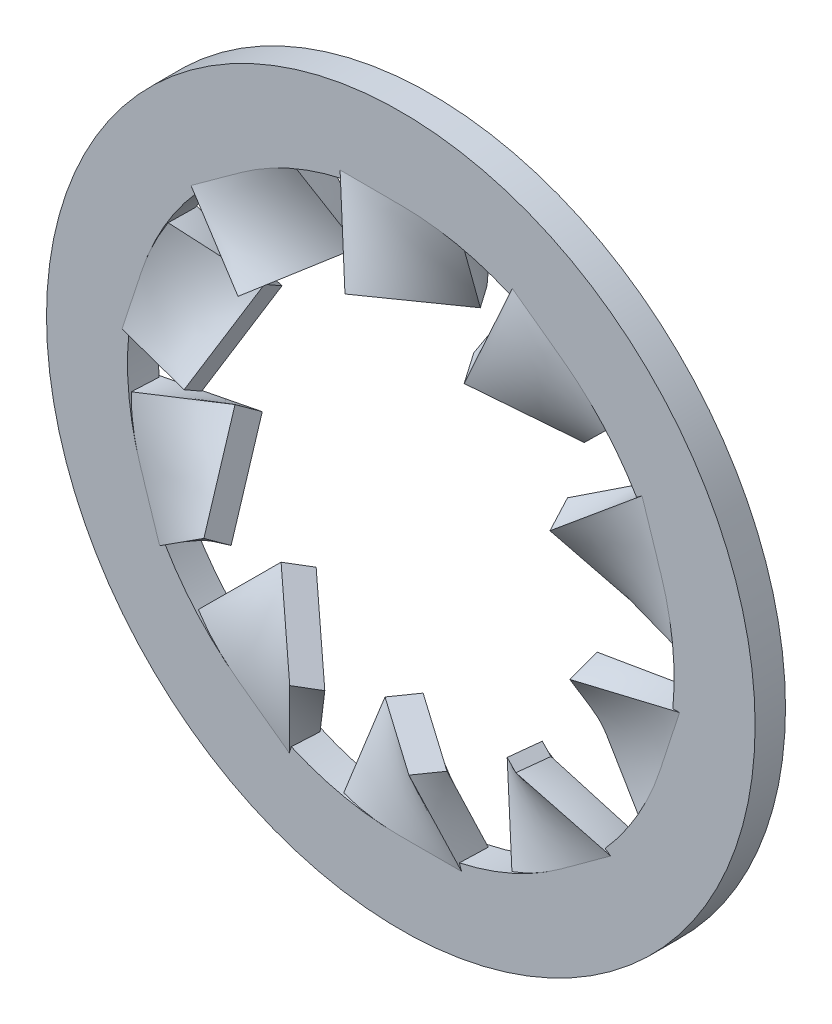
SolidWorks part; units mm, degrees
ref_plane "Front Plane" through (0, 0, 0) normal (0, 0, 1) x (1, 0, 0)
ref_plane "Top Plane" through (0, 0, 0) normal (0, 1, 0) x (1, 0, 0)
ref_plane "Right Plane" through (0, 0, 0) normal (1, 0, 0) x (0, 0, -1)
sketch "Sketch1" plane through (0, 0, 0) normal (0, 0, 1) x (1, 0, 0)
  line L0 (0, 4.826) -> (0, 8.89) construction
  circle A0 centre (0, 0) radius 4.826
  circle A1 centre (0, 0) radius 8.89
  circle A3 centre (0, 0) radius 6.858 construction
  point P6 (0, 6.858)
  point P7 (-4.826, 0)
  dimension "ID" = 9.652
  dimension "OD" = 17.78
ref_plane "Plane1" through (0, 4.826, 0) normal (0, 1, 0) x (-1, 0, 0)
ref_plane "Plane2" through (0, 6.858, 0) normal (0, 1, 0) x (-1, 0, 0)
sketch "Sketch2" plane through (0, 6.858, 0) normal (0, 1, 0) x (-1, 0, 0)
  line L0 (-1.524, 0) -> (1.524, 0) construction
  line L1 (-1.524, 0.381) -> (1.524, 0.381)
  line L2 (-1.524, 0.381) -> (-1.524, -0.381)
  line L3 (-1.524, -0.381) -> (1.524, -0.381)
  line L4 (1.524, 0.381) -> (1.524, -0.381)
  line L5 (0, 0) -> (0, 0.381) construction
  line L6 (6.858, 0) -> (-6.858, 0) construction
  dimension "D1" = 3.048
  dimension "thickness" = 0.762
sketch "Sketch3" plane through (0, 4.826, 0) normal (0, 1, 0) x (-1, 0, 0)
  line L0 (-1.1954, -0.4184) -> (-0.802, -0.9802)
  line L1 (-1.1954, -0.4184) -> (0.802, 0.9802)
  line L2 (-0.802, -0.9802) -> (1.1954, 0.4184)
  line L3 (0.802, 0.9802) -> (1.1954, 0.4184)
  line L4 (-0.9987, -0.6993) -> (0.9987, 0.6993) construction
  line L5 (-0.1967, 0.2809) -> (0.1967, -0.2809) construction
  line L7 (6.858, 0) -> (-6.858, 0) construction
  dimension "D1" = 2.4384
  dimension "D2" = 0.6858
  dimension "D3" = 35
loft "Loft2" add profiles "Sketch2", "Sketch3" connector at (-1.524, 6.858, -0.381) connector at (-1.1954, 4.826, 0.4184)
sketch "Sketch4" plane through (0, 0, 0) normal (0, 1, 0) x (1, 0, 0)
  line L0 (0, -0.381) -> (0, 0.381) construction
ref_axis "Axis1" through (0, 0, -0.381) along (0, 0, 1)
pattern_circular "CirPattern1" count 10 over 360 about axis through (0, 0, -0.381) along (0, 0, 1) of bodies 102
sketch "Sketch5" plane through (0, 0, 0) normal (0, 0, 1) x (1, 0, 0)
  circle A0 centre (0, 0) radius 8.89 construction
  circle A1 centre (0, 0) radius 6.858 construction
  circle A2 centre (0, 0) radius 8.89
  circle A3 centre (0, 0) radius 6.858
extrude "Extrude1" add sketch "Sketch5" along normal mid plane 0.762
equation "\"D1@Sketch2\" = \"thickness@Sketch2\"*4"
equation "\"D1@Sketch3\" = \"D1@Sketch2\"*.8"
equation "\"D2@Sketch3\" = \"thickness@Sketch2\"*.9"
equation "\"D1@Extrude1\" = \"thickness@Sketch2\""
